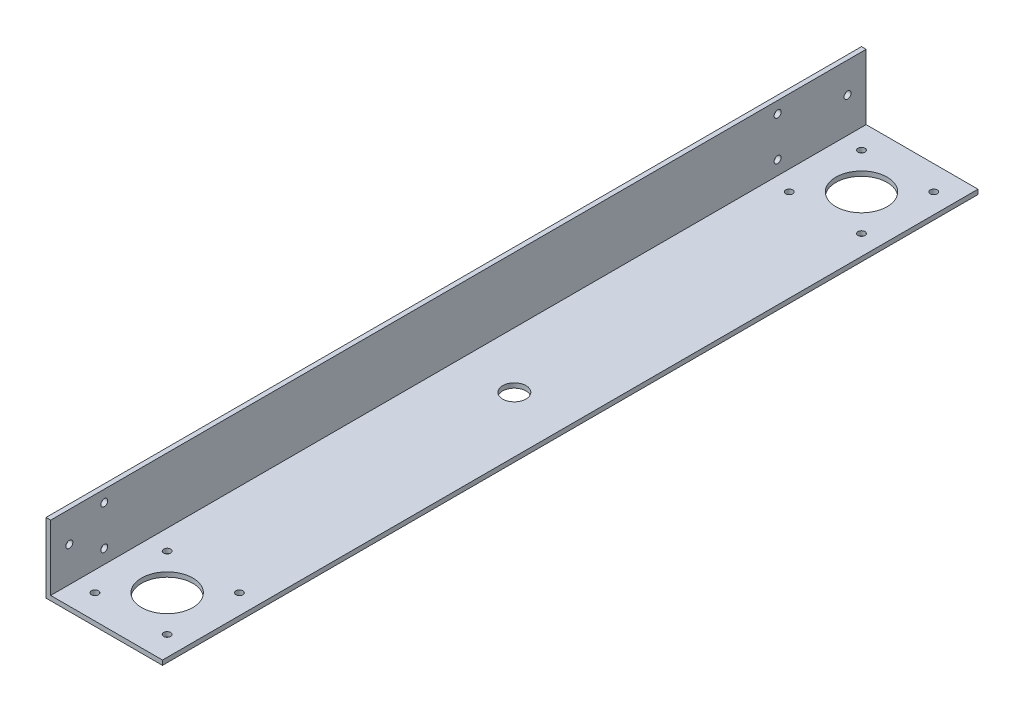
SolidWorks part; units mm, degrees
ref_plane "Front Plane" through (0, 0, 0) normal (0, 0, 1) x (1, 0, 0)
ref_plane "Top Plane" through (0, 0, 0) normal (0, 1, 0) x (1, 0, 0)
ref_plane "Right Plane" through (0, 0, 0) normal (1, 0, 0) x (0, 0, -1)
sketch "Sketch1" plane through (0, 0, 0) normal (0, 0, 1) x (1, 0, 0)
  line L0 (0, 0) -> (0, 30)
  line L1 (0, 30) -> (2, 30)
  line L2 (2, 30) -> (2, 2)
  line L3 (2, 2) -> (50, 2)
  line L4 (50, 2) -> (50, 0)
  line L5 (50, 0) -> (0, 0)
extrude "Boss-Extrude1" add sketch "Sketch1" along normal blind 350
sketch "Sketch6" plane through (0, 2, 0) normal (0, 1, 0) x (1, 0, 0)
  circle A0 centre (41.5, -339.5) radius 1.5
  circle A1 centre (10.5, -308.5) radius 1.5
  circle A2 centre (10.5, -339.5) radius 1.5
  circle A3 centre (41.5, -308.5) radius 1.5
extrude "Cut-Extrude3" cut sketch "Sketch6" against normal through all
sketch "Sketch7" plane through (0, 2, 0) normal (0, 1, 0) x (1, 0, 0)
  circle A0 centre (26, -324) radius 11
extrude "Cut-Extrude4" cut sketch "Sketch7" against normal through all
sketch "Sketch8" plane through (0, 0, 0) normal (0, -1, 0) x (-1, 0, 0)
  circle A0 centre (-26, -26) radius 11
extrude "Cut-Extrude5" cut sketch "Sketch8" against normal through all
sketch "Sketch9" plane through (0, 0, 0) normal (0, -1, 0) x (1, 0, 0)
  circle A0 centre (41.5, 41.5) radius 1.5
  circle A1 centre (10.5, 41.5) radius 1.5
  circle A2 centre (10.5, 10.5) radius 1.5
  circle A3 centre (41.5, 10.5) radius 1.5
extrude "Cut-Extrude6" cut sketch "Sketch9" against normal through all
sketch "Sketch10" plane through (0, 0, 0) normal (0, -1, 0) x (1, 0, 0)
  circle A0 centre (26, 175) radius 5
extrude "Cut-Extrude7" cut sketch "Sketch10" against normal through all
hole_wizard "Ø3.0 (3) Diameter Hole1" positions "Sketch11" profile "Sketch12" hole size "Ø3.0" standard "ISO"
sketch "Sketch11" plane through (0, 141.68, 221.138) normal (-1, 0, 0) x (0, 0, 1)
  point P0 (105.862, -133.68)
  point P1 (120.862, -124.68)
  point P2 (105.862, -116.68)
sketch "Sketch12" plane through (0, 8, 327) normal (0, 1, 0) x (0, 0, 1)
  line L0 (0, 0) -> (0, 1.999)
  line L1 (0, 1.999) -> (1.5, 1.999)
  line L2 (1.5, 1.999) -> (1.5, 0)
  line L3 (1.5, 0) -> (0, 0)
  line L4 (0, -6.35) -> (0, 107.95) construction
  dimension "Thru Hole Dia." = 3
  dimension "Thru Hole Depth" = 1.999
hole_wizard "Ø3.0 (3) Diameter Hole2" positions "Sketch13" profile "Sketch14" hole size "Ø3.0" standard "ISO"
sketch "Sketch13" plane through (0, 141.68, 221.138) normal (-1, 0, 0) x (0, 0, 1)
  point P0 (-183.138, -133.68)
  point P1 (-213.138, -124.7112)
  point P2 (-183.138, -116.68)
  point P3 (0, 0)
sketch "Sketch14" plane through (0, 8, 38) normal (0, 1, 0) x (0, 0, 1)
  line L0 (0, 0) -> (0, 1.999)
  line L1 (0, 1.999) -> (1.5, 1.999)
  line L2 (1.5, 1.999) -> (1.5, 0)
  line L3 (1.5, 0) -> (0, 0)
  line L4 (0, -6.35) -> (0, 107.95) construction
  dimension "Thru Hole Dia." = 3
  dimension "Thru Hole Depth" = 1.999
